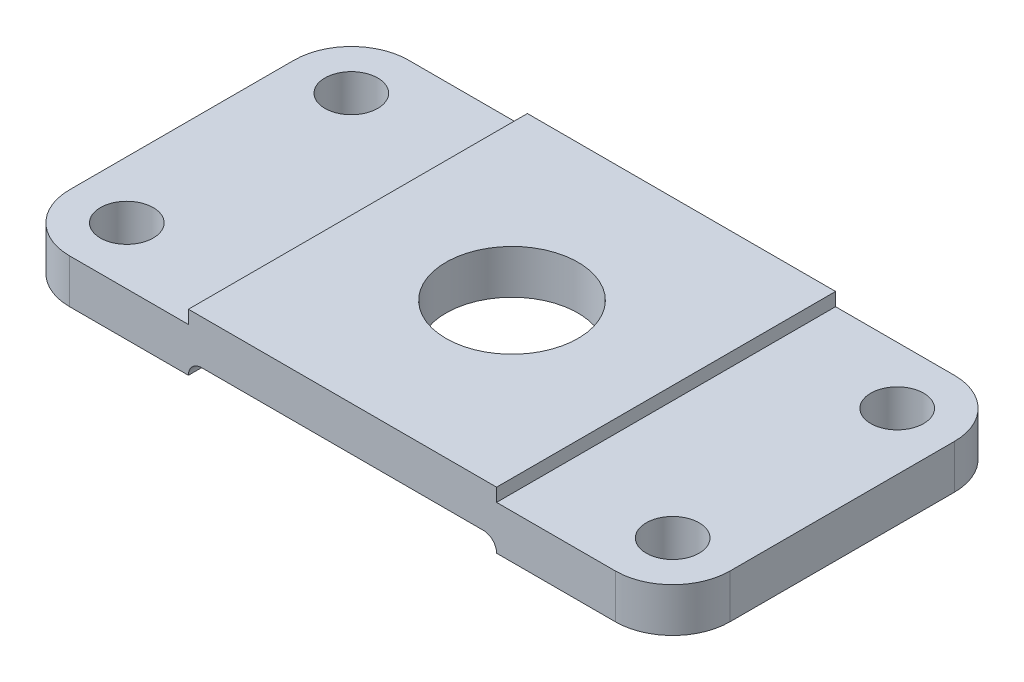
SolidWorks part; units mm, degrees
ref_plane "정면" through (0, 0, 0) normal (0, 0, 1) x (1, 0, 0)
ref_plane "윗면" through (0, 0, 0) normal (0, 1, 0) x (1, 0, 0)
ref_plane "우측면" through (0, 0, 0) normal (1, 0, 0) x (0, 0, -1)
sketch "스케치1" plane through (0, 0, 0) normal (0, 1, 0) x (1, 0, 0)
  line L1 (-62, 38.5) -> (62, 38.5)
  line L2 (-75, 25.5) -> (-75, -25.5)
  line L3 (-62, -38.5) -> (62, -38.5)
  line L4 (75, 25.5) -> (75, -25.5)
  line L5 (-75, 38.5) -> (75, -38.5) construction
  line L6 (-75, -38.5) -> (75, 38.5) construction
  arc A0 (-75, -25.5) -> (-62, -38.5) centre (-62, -25.5) ccw
  arc A1 (62, -38.5) -> (75, -25.5) centre (62, -25.5) ccw
  arc A2 (75, 25.5) -> (62, 38.5) centre (62, 25.5) ccw
  arc A3 (-62, 38.5) -> (-75, 25.5) centre (-62, 25.5) ccw
  point P0 (0, 0)
  dimension "D3" = 13
  dimension "D1" = 150
  dimension "D2" = 77
extrude "보스-돌출2" add sketch "스케치1" along normal blind 13
sketch "스케치2" plane through (0, 0, 0) normal (0, 1, 0) x (1, 0, 0)
  line L0 (0, 52.8516) -> (0, -60.2755) construction
  line L1 (-104.2107, 0) -> (111.0838, 0) construction
  circle A0 centre (-62, 25.5) radius 6
  arc A1 (-62, 38.5) -> (-75, 25.5) centre (-62, 25.5) ccw construction
  circle A2 centre (-62, -25.5) radius 6
  circle A3 centre (62, -25.5) radius 6
  circle A4 centre (62, 25.5) radius 6
  circle A5 centre (0, 0) radius 15
  dimension "D1" = 12
  dimension "D2" = 30
extrude "컷-돌출2" cut sketch "스케치2" against normal through all and the other way through all
sketch "스케치3" plane through (0, 13, 0) normal (0, 1, 0) x (1, 0, 0)
  line L0 (0, 68.0241) -> (0, -65.446) construction
  line L1 (35, 50) -> (135, 50)
  line L2 (35, 50) -> (35, -50)
  line L3 (35, -50) -> (135, -50)
  line L4 (135, 50) -> (135, -50)
  line L5 (35, 50) -> (135, -50) construction
  line L6 (35, -50) -> (135, 50) construction
  line L7 (-35, -50) -> (-135, 50) construction
  line L8 (-35, 50) -> (-135, -50) construction
  line L9 (-135, 50) -> (-135, -50)
  line L10 (-35, -50) -> (-135, -50)
  line L11 (-35, 50) -> (-35, -50)
  line L12 (-35, 50) -> (-135, 50)
  point P0 (85, 0)
  point P12 (-85, 0)
  dimension "D1" = 100
  dimension "D2" = 100
  dimension "D3" = 35
  dimension "D4" = 50
extrude "컷-돌출3" cut sketch "스케치3" against normal blind 3
sketch "스케치4" plane through (0, 0, 0) normal (0, -1, 0) x (1, 0, 0)
  line L1 (-35, 38.5) -> (35, 38.5)
  line L2 (-35, 38.5) -> (-35, -38.5)
  line L3 (-35, -38.5) -> (35, -38.5)
  line L4 (35, 38.5) -> (35, -38.5)
  line L5 (-35, 38.5) -> (35, -38.5) construction
  line L6 (-35, -38.5) -> (35, 38.5) construction
  point P0 (0, 0)
  dimension "D1" = 70
  dimension "D2" = 77
extrude "컷-돌출4" cut sketch "스케치4" against normal blind 3
fillet "필렛1" radius 3 2 edges at (-35, 3, 0) (35, 3, 0)
